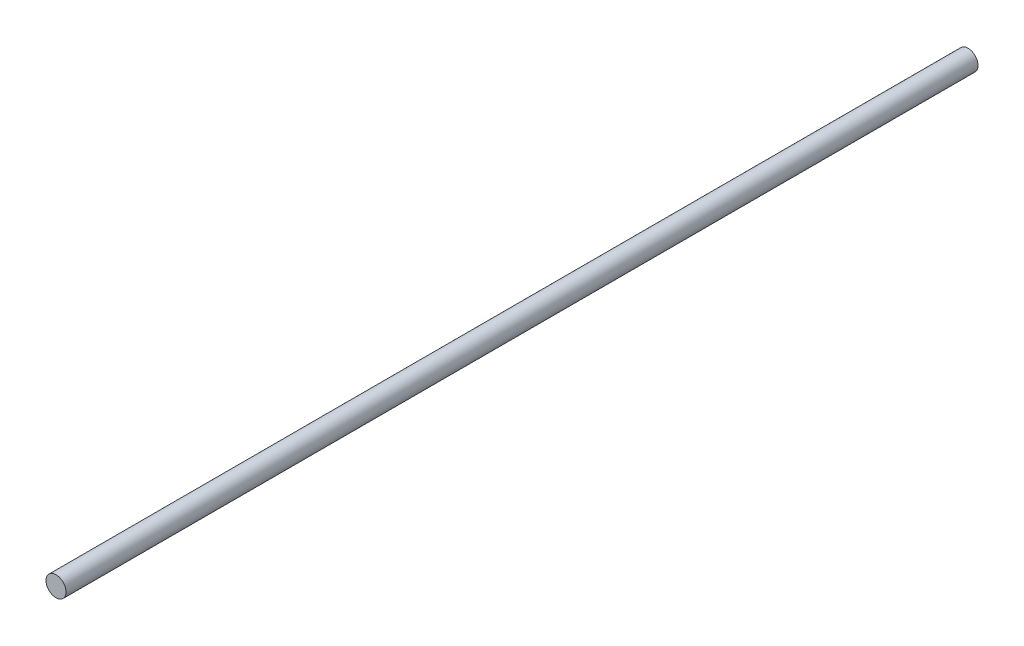
SolidWorks part; units mm, degrees
ref_plane "Front Plane" through (0, 0, 0) normal (0, 0, 1) x (1, 0, 0)
ref_plane "Top Plane" through (0, 0, 0) normal (0, 1, 0) x (1, 0, 0)
ref_plane "Right Plane" through (0, 0, 0) normal (1, 0, 0) x (0, 0, -1)
sketch "Sketch1" plane through (0, 0, 0) normal (0, 0, 1) x (1, 0, 0)
  circle A0 centre (0, 0) radius 2
  dimension "D1" = 4
extrude "Boss-Extrude1" add sketch "Sketch1" along normal blind 182.2
